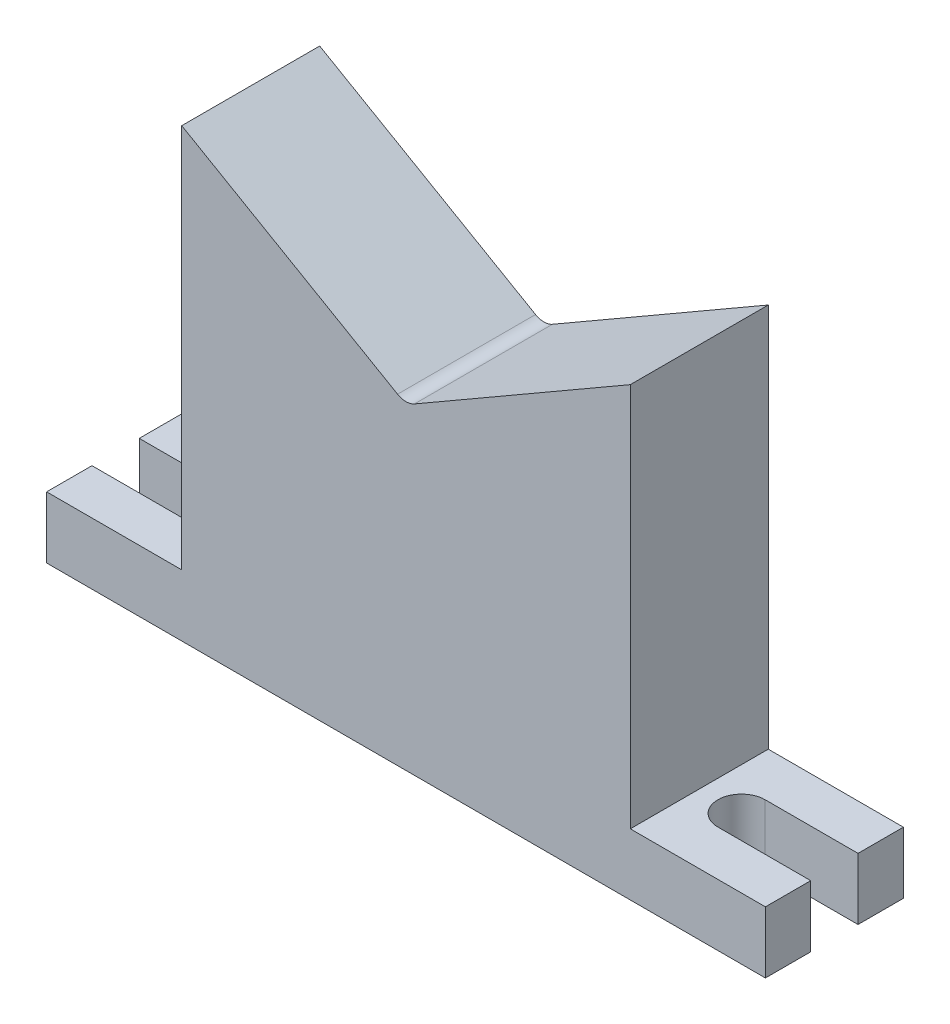
SolidWorks part; units mm, degrees
ref_plane "Front Plane" through (0, 0, 0) normal (0, 0, 1) x (1, 0, 0)
ref_plane "Top Plane" through (0, 0, 0) normal (0, 1, 0) x (1, 0, 0)
ref_plane "Right Plane" through (0, 0, 0) normal (1, 0, 0) x (0, 0, -1)
sketch "Sketch1" plane through (0, 0, 0) normal (0, 0, 1) x (1, 0, 0)
  line L0 (-33.735, 19.4769) -> (0, 0)
  line L4 (-33.735, -38.3815) -> (-33.735, 19.4769)
  line L5 (0, 0) -> (0, -47.6525) construction
  line L6 (0, 0) -> (0, 44.7273) construction
  line L8 (-33.735, -38.3815) -> (-54.055, -38.3815)
  line L11 (-54.055, -38.3815) -> (-54.055, -47.6525)
  line L12 (54.055, -38.3815) -> (54.055, -47.6525)
  line L13 (33.735, -38.3815) -> (54.055, -38.3815)
  line L14 (-38.735, 44.7273) -> (-38.735, -35.7145) construction
  line L15 (33.735, 19.4769) -> (0, 0)
  line L16 (33.735, -38.3815) -> (33.735, 19.4769)
  line L17 (-54.055, -47.6525) -> (54.055, -47.6525)
  circle A0 centre (0, 44.7273) radius 38.735 construction
  point P18 (-54.055, -43.017)
  dimension "D1" = 77.47
  dimension "D4" = 10
  dimension "D2" = 92.3798
  dimension "D3" = 9.271
  dimension "D5" = 20.32
  dimension "D6" = 120
extrude "Boss-Extrude1" add sketch "Sketch1" along normal blind 20.7518
sketch "Sketch2" plane through (0, -38.3815, 0) normal (0, 1, 0) x (1, 0, 0)
  line L0 (-68.025, -10.3759) -> (-40.085, -10.3759) construction
  line L1 (-68.025, -6.8199) -> (-40.085, -6.8199)
  line L2 (-68.025, -13.9319) -> (-40.085, -13.9319)
  line L3 (-54.055, -20.7518) -> (-54.055, 0) construction
  line L4 (-54.055, -6.8199) -> (-54.055, -13.9319)
  line L5 (-54.055, 0) -> (-54.055, -20.7518) construction
  line L6 (0, 0) -> (0, -20.7518) construction
  line L7 (0, -20.7518) -> (0, 0) construction
  line L8 (68.025, -10.3759) -> (40.085, -10.3759) construction
  line L9 (68.025, -6.8199) -> (40.085, -6.8199)
  line L10 (68.025, -13.9319) -> (40.085, -13.9319)
  line L11 (54.055, -6.8199) -> (54.055, -13.9319)
  arc A0 (-68.025, -6.8199) -> (-68.025, -13.9319) centre (-68.025, -10.3759) ccw
  arc A1 (-40.085, -13.9319) -> (-40.085, -6.8199) centre (-40.085, -10.3759) ccw
  arc A2 (68.025, -6.8199) -> (68.025, -13.9319) centre (68.025, -10.3759) cw
  arc A3 (40.085, -13.9319) -> (40.085, -6.8199) centre (40.085, -10.3759) cw
  point P2 (-54.055, -10.3759)
  point P22 (54.055, -10.3759)
  line M3 (-54.055, 0) -> (-54.055, -20.7518)
  dimension "D2" = 13.97
  dimension "D1" = 7.112
extrude "Cut-Extrude1" cut sketch "Sketch2" against normal blind 10 contours L2 A1 L1 M3 | A3 L10 L11 L9 region at (-45.6548, -38.3815, 10.3759) region at (45.6548, -38.3815, 10.3759)
fillet "Fillet1" radius 2.54 1 edges at (0, 0, 10.3759)
